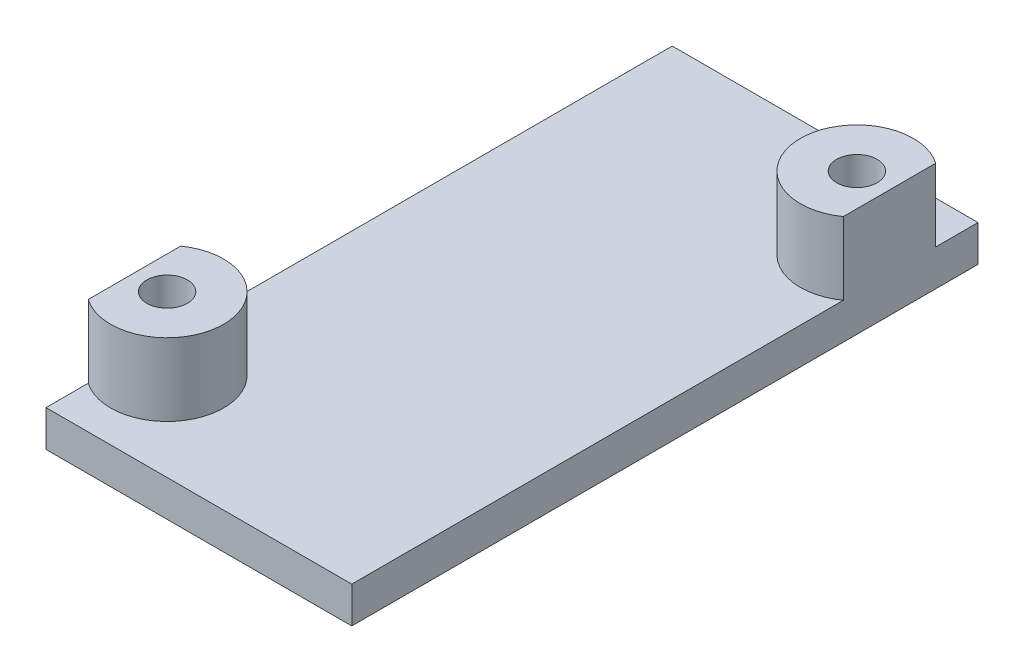
SolidWorks part; units mm, degrees
note: '?' marks a value the reader was unsure of.
material "6061-T6 (SS)"
ref_plane "Front Plane" through (0, 0, 0) normal (0, 0, 1) x (1, 0, 0)
ref_plane "Top Plane" through (0, 0, 0) normal (0, 1, 0) x (1, 0, 0)
ref_plane "Right Plane" through (0, 0, 0) normal (1, 0, 0) x (0, 0, -1)
ref_axis "Axis1" through (0, 0, 55) along (0, 0, -1)?
sketch "Sketch1" plane through (0, 0, 0) normal (0, 1, 0) x (1, 0, 0)
  line L0 (-8.291, -15.49) -> (-8.291, -21.59) construction
  line L1 (-10.541, 21.59) -> (10.541, 21.59)
  line L2 (-10.541, 21.59) -> (-10.541, -21.59)
  line L3 (-10.541, -21.59) -> (10.541, -21.59)
  line L4 (10.541, 21.59) -> (10.541, -21.59)
  line L5 (-10.541, 21.59) -> (10.541, -21.59) construction
  line L6 (-10.541, -21.59) -> (10.541, 21.59) construction
  line L7 (-8.291, -15.49) -> (-10.541, -15.49) construction
  line L8 (8.291, 15.49) -> (8.291, 21.59) construction
  line L9 (8.291, 15.49) -> (10.541, 15.49) construction
  circle A0 centre (8.291, 15.49) radius 1.4 construction
  circle A1 centre (-8.291, -15.49) radius 1.4 construction
  point P0 (0, 0)
  point P12 (-5.4197, -16.4412)
  dimension "D3" = 2.8
  dimension "D1" = 21.082
  dimension "D2" = 43.18
  dimension "D4" = 6.1
  dimension "D5" = 2.25
  dimension "D6" = 6.1
  dimension "D7" = 2.25
extrude "Boss-Extrude1" add sketch "Sketch1" along normal blind 2.5
sketch "Sketch2" plane through (0, 2.5, 0) normal (0, 1, 0) x (1, 0, 0)
  line L2 (10.541, 15.9016) -> (10.541, 14.0704)
  line L3 (10.541, 21.59) -> (10.541, -21.59) construction
  circle A0 centre (8.291, 15.49) radius 1.4 construction
  circle A2 centre (8.291, 15.49) radius 1.4
  circle A6 centre (-8.291, -15.49) radius 1.4 construction
  circle A7 centre (-8.291, -15.49) radius 1.4
  circle A8 centre (-8.291, -15.49) radius 3.9
  circle A9 centre (8.291, 15.49) radius 3.9
  dimension "D1" = 2.5
extrude "Boss-Extrude2" add sketch "Sketch2" along normal blind 5 contours A8 A7 | A9 A2
